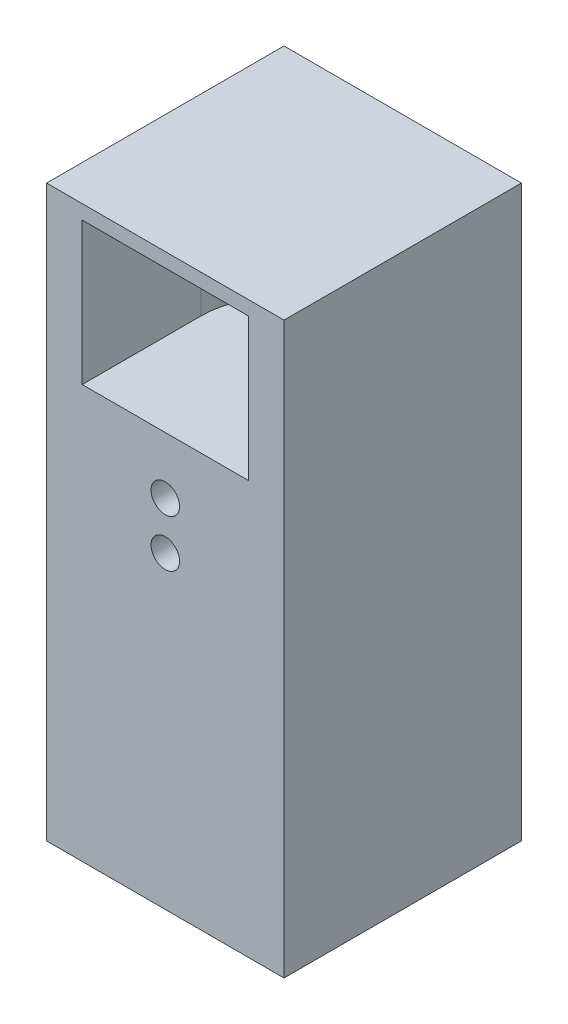
SolidWorks part; units mm, degrees
ref_plane "Front Plane" through (0, 0, 0) normal (0, 0, 1) x (1, 0, 0)
ref_plane "Top Plane" through (0, 0, 0) normal (0, 1, 0) x (1, 0, 0)
ref_plane "Right Plane" through (0, 0, 0) normal (1, 0, 0) x (0, 0, -1)
sketch "Sketch1" plane through (0, 0, 0) normal (0, 0, 1) x (1, 0, 0)
  line L0 (0, 43.5154) -> (0, -35.6563) construction
  line L1 (-41.1964, 0) -> (37.9753, 0) construction
sketch "Sketch2" plane through (0, 0, 0) normal (1, 0, 0) x (0, 0, -1)
  line L0 (41.6044, 0) -> (-41.6044, 0) construction
sketch "Sketch5" plane through (0, 0, 0) normal (0, 1, 0) x (1, 0, 0)
  line L0 (100.33, 25.6173) -> (120.65, 25.6173)
  line L1 (0, 127) -> (127, 127)
  line L2 (0, 127) -> (0, 0)
  line L3 (0, 0) -> (127, 0)
  line L4 (127, 127) -> (127, 0)
  line L5 (6.35, 25.6173) -> (26.67, 25.6173)
  line L6 (6.35, 25.6173) -> (6.35, 5.2973)
  line L7 (6.35, 5.2973) -> (26.67, 5.2973)
  line L8 (26.67, 25.6173) -> (26.67, 5.2973)
  line L9 (100.33, 25.6173) -> (100.33, 5.2973)
  line L10 (100.33, 5.2973) -> (120.65, 5.2973)
  line L11 (120.65, 25.6173) -> (120.65, 5.2973)
  line L12 (100.33, 120.65) -> (120.65, 120.65)
  line L13 (100.33, 120.65) -> (100.33, 100.33)
  line L14 (100.33, 100.33) -> (120.65, 100.33)
  line L15 (120.65, 120.65) -> (120.65, 100.33)
  line L16 (6.35, 120.65) -> (26.67, 120.65)
  line L17 (6.35, 120.65) -> (6.35, 100.33)
  line L18 (6.35, 100.33) -> (26.67, 100.33)
  line L19 (26.67, 120.65) -> (26.67, 100.33)
  point P9 (0, 0)
  point P10 (0, 0)
  point P11 (0, 0)
  point P24 (0, 0)
  point P25 (0, 0)
  dimension "D1" = 127
  dimension "D2" = 127
  dimension "D3" = 20.32
  dimension "D4" = 20.32
  dimension "D5" = 6.35
  dimension "D6" = 5.2973
  dimension "D9" = 6.35
  dimension "D10" = 6.35
  dimension "D11" = 6.35
  dimension "D7" = 2
  dimension "D8" = 2
extrude "Boss-Extrude1" add sketch "Sketch5" along normal blind 304.8 contours L4 L1 L2 L3 L5 L8 L7 L6 L0 L11 L10 L9 L12 L15 L14 L13 L16 L19 L18 L17 | L11 L0 L9 L10 | L15 L12 L13 L14 | L8 L5 L6 L7 | L19 L16 L17 L18 region at (110.49, 0, -15.4573) region at (63.5, 0, -63.56) region at (16.51, 0, -15.4573) region at (110.49, 0, -110.49) region at (16.51, 0, -110.49)
sketch "Sketch6" plane through (0, 0, 0) normal (0, 1, 0) x (1, 0, 0)
  circle A0 centre (63.5, 63.5) radius 44.45
  point P2 (0, 0)
  point P3 (69.0141, 65.585)
  dimension "D1" = 88.9
  dimension "D2" = 63.5
  dimension "D3" = 63.5
extrude "Cut-Extrude1" cut sketch "Sketch6" along normal blind 203.2 contours A0
extrude "Cut-Extrude2" cut sketch "Sketch5<3>" along normal blind 25.4 contours L8 L5 L6 L7 | L11 L0 L9 L10 | L15 L12 L13 L14 | L19 L16 L17 L18 region at (110.49, 0, -15.4573) region at (16.51, 0, -15.4573) region at (110.49, 0, -110.49) region at (16.51, 0, -110.49)
sketch "Sketch5<3>" plane through (0, 0, 0) normal (0, 1, 0) x (1, 0, 0) same geometry as "Sketch5"
sketch3d "3DSketch2" plane through (0, 0, 0) normal (0, 0, 1) x (1, 0, 0)
  dimension "D1" = 7.62
sketch "Sketch7" plane through (0, 297.18, 0) normal (0, 1, 0) x (1, 0, 0)
  line L3 (107.95, 63.5) -> (107.95, -124.5968)
  line L4 (107.95, -124.5968) -> (19.05, -124.5968)
  line L5 (19.05, 63.5) -> (19.05, -124.5968)
  arc A0 (107.95, 63.5) -> (19.05, 63.5) centre (63.5, 63.5) ccw
  point P1 (50.8, 0)
  point P2 (0, 0)
  point P3 (51.5995, 52.957)
  point P8 (50.8, 0)
  point P9 (0, 0)
  point P10 (0, 0)
  point P12 (0, 0)
  point P13 (35.9464, -75.9597)
  point P14 (0, 0)
  point P15 (19.05, 63.5)
  point P16 (63.5, 63.5)
  point P17 (0, 0)
  dimension "D1" = 44.45
  dimension "D2" = 63.5
  dimension "D3" = 63.5
extrude "Cut-Extrude3" cut sketch "Sketch7" against normal blind 76.2
sketch "Sketch9" plane through (0, 0, 0) normal (0, 0, 1) x (1, 0, 0)
  circle A0 centre (63.5, 190.5) radius 7.62
  circle A1 centre (63.5, 165.1) radius 7.62
  dimension "D1" = 15.24
  dimension "D2" = 63.5
  dimension "D3" = 114.3
  dimension "D4" = 2
extrude "Cut-Extrude4" cut sketch "Sketch9" against normal blind 56.642
